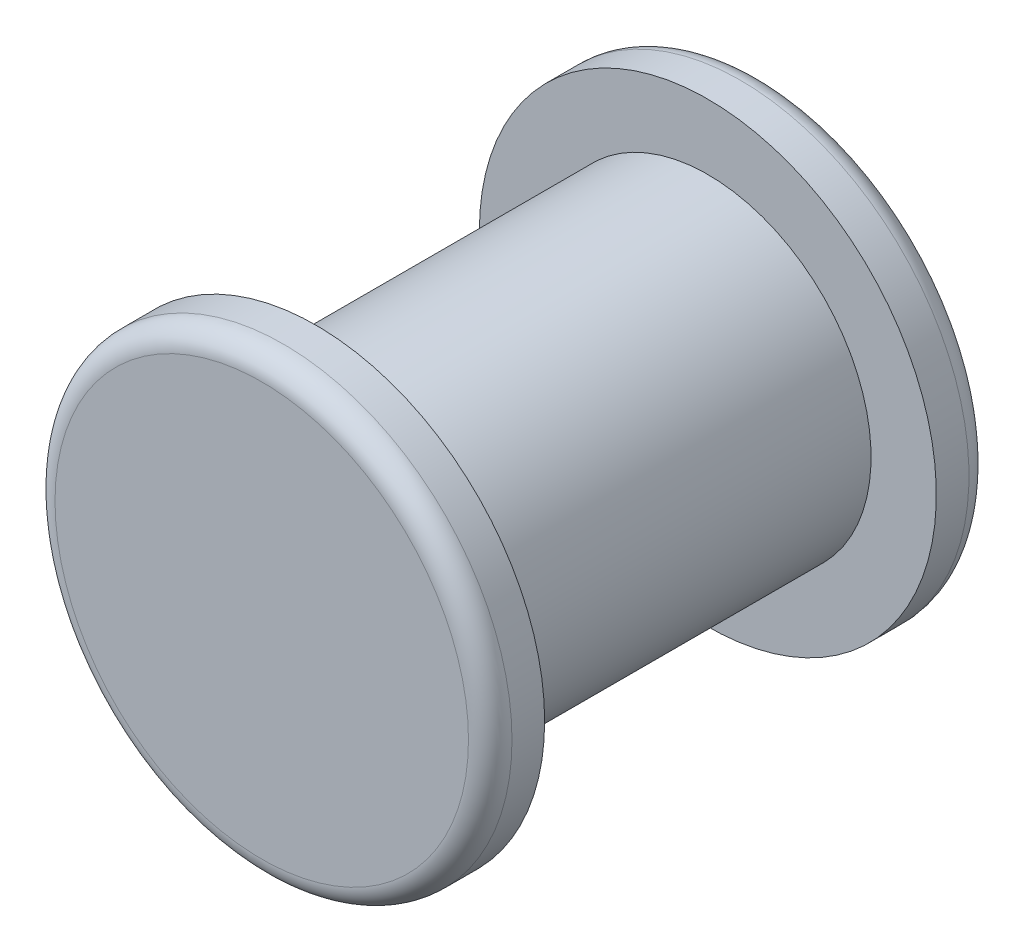
SolidWorks part; units mm, degrees
ref_plane "Front Plane" through (0, 0, 0) normal (0, 0, 1) x (1, 0, 0)
ref_plane "Top Plane" through (0, 0, 0) normal (0, 1, 0) x (1, 0, 0)
ref_plane "Right Plane" through (0, 0, 0) normal (1, 0, 0) x (0, 0, -1)
sketch "Sketch1" plane through (0, 0, 0) normal (0, 0, 1) x (1, 0, 0)
  circle A0 centre (0, 0) radius 75
  dimension "D1" = 150
extrude "Boss-Extrude1" add sketch "Sketch1" along normal blind 180 contours A0
sketch "Sketch2" plane through (0, 0, 180) normal (0, 0, 1) x (1, 0, 0)
  circle A0 centre (0, 0) radius 105
  dimension "D1" = 210
extrude "Boss-Extrude2" add sketch "Sketch2" along normal blind 25
sketch "Sketch3" plane through (0, 0, 0) normal (0, 0, -1) x (-1, 0, 0)
  circle A0 centre (0, 0) radius 105
  dimension "D1" = 210
extrude "Boss-Extrude3" add sketch "Sketch3" along normal blind 25
fillet "Fillet1" radius 10 2 edges at (105, 0, 205) (-105, 0, -25)
